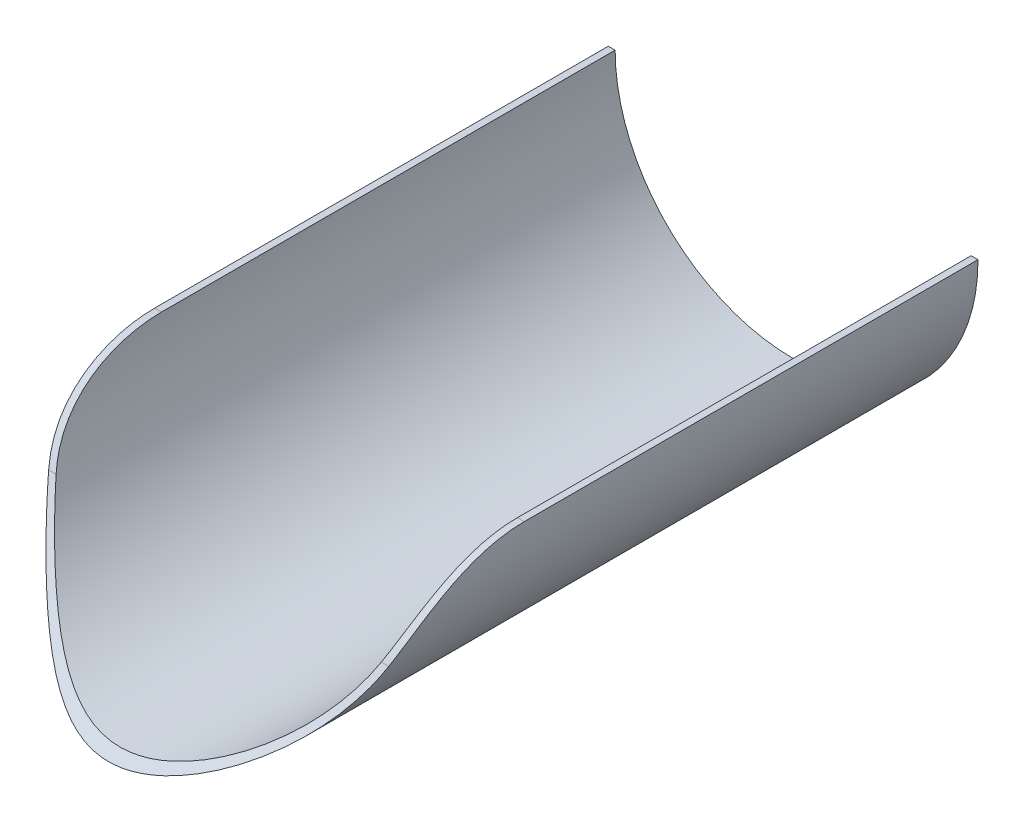
SolidWorks part; units mm, degrees
material "PLA"
ref_plane "Front Plane" through (0, 0, 0) normal (0, 0, 1) x (1, 0, 0)
ref_plane "Top Plane" through (0, 0, 0) normal (0, 1, 0) x (1, 0, 0)
ref_plane "Right Plane" through (0, 0, 0) normal (1, 0, 0) x (0, 0, -1)
sketch "Sketch1" plane through (0, 0, 0) normal (0, 0, 1) x (1, 0, 0)
  line L0 (-64.0179, 0) -> (70.1786, 0) construction
  arc A0 (-54, 0) -> (54, 0) centre (0, 0) ccw
  dimension "D1" = 108
extrude "Extrude-Thin1" add sketch "Sketch1" against normal blind 200 thin thin type one direction reverse wall 2
sketch "Sketch2" plane through (0, 0, 0) normal (1, 0, 0) x (0, 0, -1)
  line L1 (0, 0) -> (0, -54) construction
  line L2 (0, 0) -> (0, -54)
  line L4 (200, 0) -> (0, 0) construction
  line L5 (0, 0) -> (40, 0)
  arc A0 (0, -54) -> (40, 0) centre (-40.1059, 17.5229) ccw
  dimension "D2" = 82
  dimension "D1" = 40
extrude "Cut-Extrude1" cut sketch "Sketch2" against normal through all both and the other way through all
fillet "Fillet1" radius 40 2 edges at (53, 0, -40) (-53, 0, -40)
